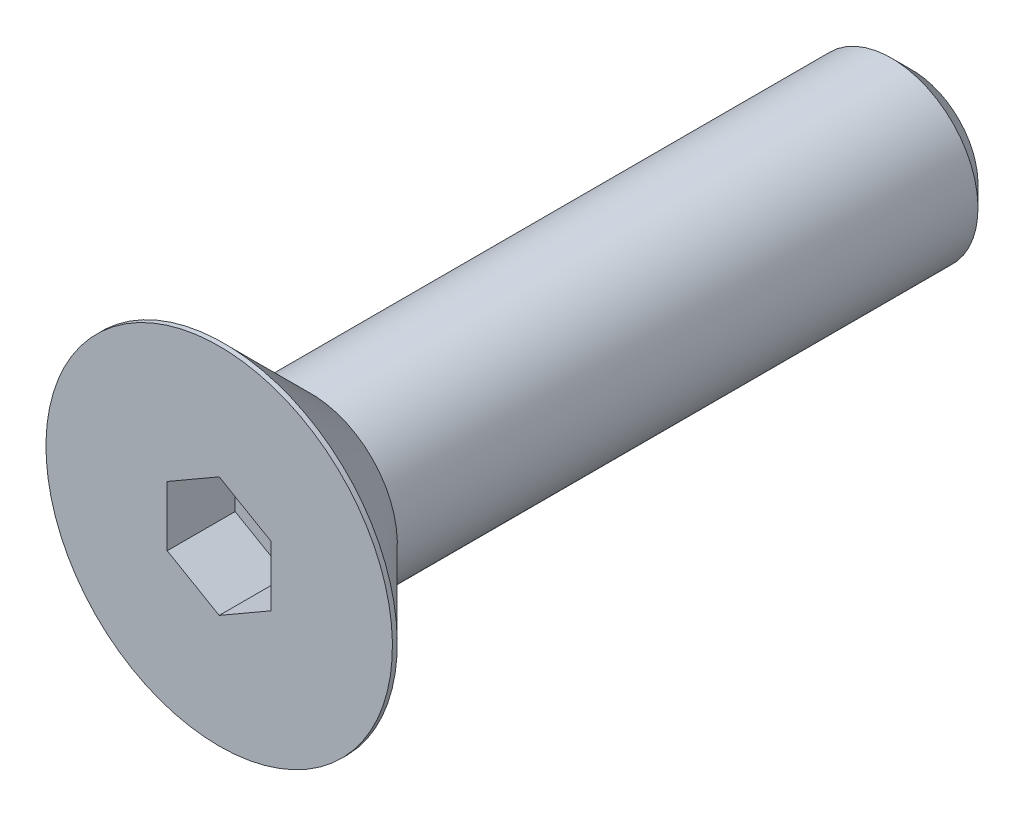
SolidWorks part; units mm, degrees
material "Chrome Stainless Steel"
ref_plane "Front" through (0, 0, 0) normal (0, 0, 1) x (1, 0, 0)
ref_plane "Top" through (0, 0, 0) normal (0, 1, 0) x (1, 0, 0)
ref_plane "Right" through (0, 0, 0) normal (1, 0, 0) x (0, 0, -1)
sketch "Sketch11" plane through (0, 0, 0) normal (1, 0, 0) x (0, 0, -1)
  line L0 (-10, 5) -> (10, 5) construction
  line L5 (-10, 5) -> (-10, -5) construction
  line L6 (10, 2.5) -> (10, -2.5) construction
  line L7 (-9.99, 1.5) -> (-9.99, -1.5) construction
  line L8 (9.95, 2.5866) -> (10.75, 2.5866) construction
  line L9 (10.75, 2.5866) -> (10.35, 1.8938) construction
  line L10 (10.35, 1.8938) -> (9.95, 2.5866) construction
  line L11 (10.3, 1.9804) -> (10.4, 1.9804) construction
  line L12 (10.35, 1.9804) -> (10.35, 1.8938) construction
  line L13 (9.975, 2.5433) -> (10.725, 2.5433) construction
  line L14 (10.35, 2.5866) -> (10.35, 2.5) construction
  line L15 (10, 2.5) -> (10.7, 2.5) construction
  line L17 (-9.86, 5) -> (-4.86, 0) construction
  line L18 (-4.86, 0) -> (-9.86, -5) construction
  point P3 (-7.2, 5)
  point P8 (0, 5)
  point P21 (10.35, 2.5433)
  point P26 (-10, 0)
  point P28 (-9.99, 0)
  point P29 (10, 0)
  dimension "Length" = 20
  dimension "Head Diameter" = 10
  dimension "Thread Major Diameter" = 5
  dimension "Head Height" = 2.8
  dimension "Drive Size" = 3
  dimension "Thread Pitch" = 0.8
  dimension "D1" = 0.1
  dimension "D2" = 0.01
  dimension "D3" = 0.14
  dimension "Countersink Angle" = 90
sketch "Sketch1" plane through (0, 0, 0) normal (1, 0, 0) x (0, 0, -1)
  line L2 (-7.2, 2.5) -> (10, 2.5)
  line L3 (10, 2.5) -> (10, 0)
  line L4 (-8.04, 2.5) -> (-8.04, 0)
  line L5 (-7.2, 2.5) -> (-8.04, 2.5)
  line L6 (-10, 5) -> (-10, -5) construction
  line L7 (10, 2.5) -> (10, -2.5) construction
  line L8 (-8.04, 0) -> (10, 0)
  dimension "D1" = 1.96
revolve "Revolve1" add sketch "Sketch1" angle 360 mid plane about L8
chamfer "Chamfer1" distance 0.6 angle 45 1 edges at (0, -2.5, -10)
sketch "Sketch7" plane through (0, 0, 0) normal (1, 0, 0) x (0, 0, -1)
  line L2 (-10, 5) -> (-9.86, 5)
  line L5 (-7.2, 2.34) -> (-7.2, 0)
  line L6 (-10, 5) -> (-10, 0)
  line L8 (-10, 5) -> (-10, -5) construction
  line L9 (-10, 0) -> (-7.2, 0)
  line L12 (-9.86, 5) -> (-7.2, 2.34)
  line L13 (-9.86, 5) -> (-4.86, 0) construction
revolve "Revolve2" add sketch "Sketch7" angle 360 mid plane about L9 region at (0, 1.9545, 8.7736)
ref_plane "Plane1" through (0, 0, 7.2) normal (0, 0, 1) x (1, 0, 0)
sketch "Sketch5" plane through (0, 0, 10) normal (0, 0, 1) x (1, 0, 0)
  line L1 (1.5, -0.866) -> (1.5, 0.866)
  line L2 (1.5, 0.866) -> (0, 1.7321)
  line L3 (0, 1.7321) -> (-1.5, 0.866)
  line L4 (-1.5, 0.866) -> (-1.5, -0.866)
  line L5 (-1.5, -0.866) -> (0, -1.7321)
  line L6 (0, -1.7321) -> (1.5, -0.866)
  circle A0 centre (0, 0) radius 1.5 construction
extrude "Cut-Extrude2" cut sketch "Sketch5" against normal blind 1.96
sketch "Sketch6" plane through (0, 0, 10) normal (0, 0, -1) x (-1, 0, 0)
  circle A0 centre (0, 0) radius 1.7321
extrude "Cut-Extrude3" [suppressed] cut sketch "Sketch6" along normal blind 1.96 draft 45
sketch "Sketch12" [suppressed] plane through (0, 0, -10) normal (0, 0, -1) x (-1, 0, 0)
  circle A0 centre (0, 0) radius 2.5 construction
  circle A1 centre (0, 0) radius 2.5
curve "Helix/Spiral1" [suppressed] pitch 0.8 height 20 turns 25
sketch "Sketch13" [suppressed] plane through (0, 0, 0) normal (1, 0, 0) x (0, 0, -1)
  line L0 (9.975, 2.5433) -> (10.725, 2.5433)
  line L1 (10.725, 2.5433) -> (10.4, 1.9804)
  line L2 (10.4, 1.9804) -> (10.3, 1.9804)
  line L3 (10.3, 1.9804) -> (9.975, 2.5433)
sweep "Cut-Sweep1" [suppressed] cut profiles "Sketch13" path "Helix/Spiral1"
combine bodies "Combine1" [suppressed] operation type add bodies to combine 113 127
equation "\"D1@Chamfer1\"=\"Thread Pitch@Sketch11\" * .75"
equation "\"D1@Cut-Extrude2\"= \"Head Height@Sketch11\" * .7"
equation "\"D1@Cut-Extrude3\" = \"D1@Cut-Extrude2\""
equation "\"D1@Sketch11\"=\"Thread Pitch@Sketch11\"/8"
equation "\"D3@Sketch11\"=\"Head Height@Sketch11\"*.05"
equation "\"D4@Helix/Spiral1\"=\"Thread Pitch@Sketch11\""
equation "\"D1@Sketch1\"=\"Head Height@Sketch11\"*.7"
equation "\"D3@Helix/Spiral1\"=\"Length@Sketch11\""
